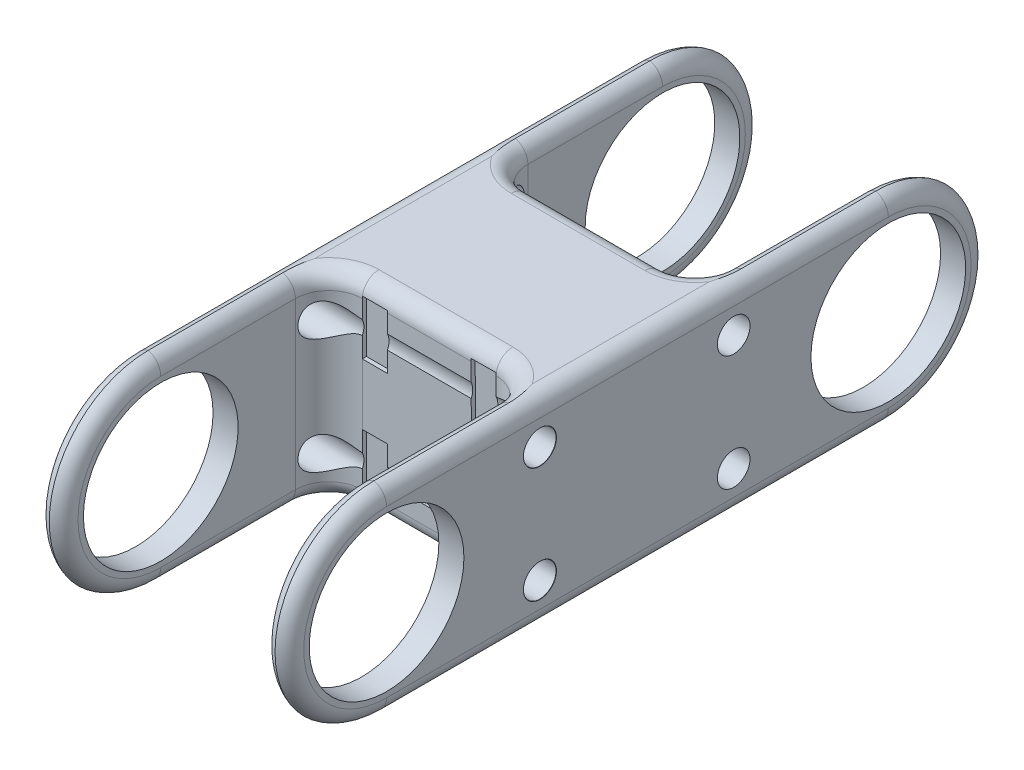
SolidWorks part; units mm, degrees
ref_plane "Front Plane" through (0, 0, 0) normal (0, 0, 1) x (1, 0, 0)
ref_plane "Top Plane" through (0, 0, 0) normal (0, 1, 0) x (1, 0, 0)
ref_plane "Right Plane" through (0, 0, 0) normal (1, 0, 0) x (0, 0, -1)
sketch "Sketch1" plane through (0, 0, 0) normal (1, 0, 0) x (0, 0, -1)
  line L0 (0, 11.9) -> (60, 11.9)
  line L1 (0, -11.9) -> (60, -11.9)
  line L2 (30, 11.9) -> (30, -11.9) construction
  circle A0 centre (0, 0) radius 9.25
  arc A1 (0, 11.9) -> (0, -11.9) centre (0, 0) ccw
  circle A2 centre (60, 0) radius 9.25
  arc A3 (60, 11.9) -> (60, -11.9) centre (60, 0) cw
  dimension "D1" = 18.5
  dimension "D2" = 23.8
  dimension "D3" = 60
extrude "Boss-Extrude1" add sketch "Sketch1" along normal blind 30
sketch "Sketch2" plane through (0, 11.9, 0) normal (0, 1, 0) x (1, 0, 0)
  line L0 (0, -11.9) -> (30, -11.9) construction
  line L1 (3, -11.9) -> (27, -11.9)
  line L2 (3, -11.9) -> (3, 20.1)
  line L3 (3, 20.1) -> (27, 20.1)
  line L4 (27, -11.9) -> (27, 20.1)
  line L5 (0, 30) -> (30, 30) construction
  line L6 (0, 60) -> (0, 0) construction
  line L7 (30, 60) -> (30, 0) construction
  line L8 (3, 39.9) -> (27, 39.9)
  line L9 (27, 71.9) -> (27, 39.9)
  line L10 (3, 71.9) -> (27, 71.9)
  line L11 (3, 71.9) -> (3, 39.9)
  dimension "D1" = 32
  dimension "D2" = 3
  dimension "D3" = 3
extrude "Cut-Extrude1" cut sketch "Sketch2" against normal through all
ref_plane "Plane1" through (0, 0, -30) normal (0, 0, 1) x (1, 0, 0)
fillet "Fillet1" radius 4 4 edges at (27, 0, -20.1) (3, 0, -20.1) (27, 0, -39.9) (3, 0, -39.9)
hole_wizard "M3.5 Clearance Hole1" positions "Sketch3" profile "Sketch4" hole size "M3.5" standard "ANSI Metric" end condition through all
sketch "Sketch3" plane through (0, 0, 0) normal (-1, 0, 0) x (0, 0, 1)
  point P0 (-41.511, -6.9)
  point P3 (-41.511, 6.9)
sketch "Sketch4" plane through (0, -6.9, -41.511) normal (0, 1, 0) x (0, 0, 1)
  line L0 (0, 0) -> (0, 30)
  line L1 (0, 30) -> (1.95, 30)
  line L2 (1.95, 30) -> (1.95, 0.025)
  line L3 (1.95, 0.025) -> (1.975, 0)
  line L5 (1.975, 0) -> (0, 0)
  line L6 (-1.95, 0.025) -> (-1.975, 0) construction
  line L11 (0, -6.35) -> (0, 107.95) construction
  dimension "Thru Hole Dia." = 3.9
  dimension "Thru Hole Depth" = 30
  dimension "Near C'Sink Dia." = 3.95
  dimension "Near C'Sink Angle" = 90
sketch "Sketch5" plane through (0, 0, -39.9) normal (0, 0, -1) x (-1, 0, 0)
  line L0 (-23, 5.8014) -> (-23, -5.8014) construction
  line L1 (-23, 0) -> (-7, 0) construction
  line L2 (-7, -5.8014) -> (-7, 5.8014) construction
  line B0 (-23, -3.65) -> (-23, -10.15)
  line B1 (-23, -3.65) -> (-20, -3.65)
  line B2 (-20, -3.65) -> (-20, -10.15)
  line B3 (-23, -10.15) -> (-20, -10.15)
  line B4 (-23, 0) -> (-7, 0) construction
  line B5 (-14.9675, -0.1255) -> (-15, -8.8352) construction
  line B6 (-7.01, -10.2096) -> (-10.0099, -10.1872)
  line B7 (-9.9615, -3.6874) -> (-10.0099, -10.1872)
  line B8 (-6.9616, -3.7098) -> (-9.9615, -3.6874)
  line B9 (-6.9616, -3.7098) -> (-7.01, -10.2096)
  line B10 (-6.9616, 3.7098) -> (-7.01, 10.2096)
  line B11 (-6.9616, 3.7098) -> (-9.9615, 3.6874)
  line B12 (-9.9615, 3.6874) -> (-10.0099, 10.1872)
  line B13 (-7.01, 10.2096) -> (-10.0099, 10.1872)
  line B14 (-23, 10.15) -> (-20, 10.15)
  line B15 (-20, 3.65) -> (-20, 10.15)
  line B16 (-23, 3.65) -> (-20, 3.65)
  line B17 (-23, 3.65) -> (-23, 10.15)
sketch_block_instance "Block1-1"
sketch_block "Block1" parameters "D1"=3, "D2"=6.5
sketch "Sketch6" plane through (30, 0, 0) normal (-1, 0, 0) x (0, 0, 1)
  line L0 (-39.536, -6.9) -> (-43.486, -6.9) construction
  circle A0 centre (-41.511, -6.9) radius 1.975 construction
extrude "Cut-Extrude2" cut sketch "Sketch5" against normal blind 0.5
hole_wizard "M3.5 Clearance Hole2" positions "Sketch9" profile "Sketch8" hole size "M3.5" standard "ANSI Metric" end condition through all
sketch "Sketch9" plane through (30, 0, 0) normal (1, 0, 0) x (0, 0, -1)
  point P0 (18.34, 6.9)
  point P3 (18.34, -6.9)
sketch "Sketch8" plane through (30, 6.9, -18.34) normal (0, 1, 0) x (0, 0, -1)
  line L0 (0, 0) -> (0, 30)
  line L1 (0, 30) -> (1.95, 30)
  line L2 (1.95, 30) -> (1.95, 0.025)
  line L3 (1.95, 0.025) -> (1.975, 0)
  line L5 (1.975, 0) -> (0, 0)
  line L6 (-1.95, 0.025) -> (-1.975, 0) construction
  line L11 (0, -6.35) -> (0, 107.95) construction
  dimension "Thru Hole Dia." = 3.9
  dimension "Thru Hole Depth" = 30
  dimension "Near C'Sink Dia." = 3.95
  dimension "Near C'Sink Angle" = 90
sketch "Sketch10" plane through (0, 0, -20.1) normal (0, 0, 1) x (1, 0, 0)
  line L0 (-1.0691, -12.5585) -> (14.9309, -12.5585) construction
  line L1 (23, 0) -> (7, 0) construction
  line L2 (23, -6.0604) -> (23, 6.0604) construction
  line L3 (7, 6.0604) -> (7, -6.0604) construction
  point P8 (23, 0)
  line B0 (7, -3.65) -> (7, -10.15)
  line B1 (7, -3.65) -> (10, -3.65)
  line B2 (10, -3.65) -> (10, -10.15)
  line B3 (7, -10.15) -> (10, -10.15)
  line B4 (22.99, -10.2096) -> (19.9901, -10.1872)
  line B5 (20.0385, -3.6874) -> (19.9901, -10.1872)
  line B6 (23.0384, -3.7098) -> (20.0385, -3.6874)
  line B7 (23.0384, -3.7098) -> (22.99, -10.2096)
  line B8 (23.0384, 3.7098) -> (22.99, 10.2096)
  line B9 (23.0384, 3.7098) -> (20.0385, 3.6874)
  line B10 (20.0385, 3.6874) -> (19.9901, 10.1872)
  line B11 (22.99, 10.2096) -> (19.9901, 10.1872)
  line B12 (7, 10.15) -> (10, 10.15)
  line B13 (10, 3.65) -> (10, 10.15)
  line B14 (7, 3.65) -> (10, 3.65)
  line B15 (7, 3.65) -> (7, 10.15)
sketch_block_instance "Block1-2"
extrude "Cut-Extrude3" cut sketch "Sketch10" against normal blind 0.5
fillet "Fillet2" radius 2 32 edges at (0, 0, -71.9) (0, -11.9, -30) (0, 0, 11.9) (3, 0, -71.9) (3, -11.9, -51.95) (4.1716, -11.9, -41.0716) (15, -11.9, -39.9) (25.8284, -11.9, -41.0716) (27, -11.9, -51.95) (27, 0, -71.9) (30, 0, -71.9) (30, -11.9, -30) (30, 0, 11.9) (27, 0, 11.9) (27, -11.9, -8.05) (25.8284, -11.9, -18.9284) (15, -11.9, -20.1) (4.1716, -11.9, -18.9284) (3, -11.9, -8.05) (3, 0, 11.9) (0, 11.9, -30) (3, 11.9, -51.95) (4.1716, 11.9, -41.0716) (15, 11.9, -39.9) (25.8284, 11.9, -41.0716) (27, 11.9, -51.95) (30, 11.9, -30) (27, 11.9, -8.05) (25.8284, 11.9, -18.9284) (15, 11.9, -20.1) (4.1716, 11.9, -18.9284) (3, 11.9, -8.05)
hole_wizard "M3.5 Clearance Hole3" positions "Sketch11" profile "Sketch12" hole size "M3.5" standard "ANSI Metric" end condition through all
sketch "Sketch11" plane through (30, 0, 0) normal (1, 0, 0) x (0, 0, -1)
  point P0 (18.34, 6.9)
  point P3 (18.34, -6.9)
sketch "Sketch12" plane through (30, 6.9, -18.34) normal (0, 1, 0) x (0, 0, -1)
  line L0 (0, 0) -> (0, 30)
  line L1 (0, 30) -> (1.95, 30)
  line L2 (1.95, 30) -> (1.95, 0.025)
  line L3 (1.95, 0.025) -> (1.975, 0)
  line L5 (1.975, 0) -> (0, 0)
  line L6 (-1.95, 0.025) -> (-1.975, 0) construction
  line L11 (0, -6.35) -> (0, 107.95) construction
  dimension "Thru Hole Dia." = 3.9
  dimension "Thru Hole Depth" = 30
  dimension "Near C'Sink Dia." = 3.95
  dimension "Near C'Sink Angle" = 90
